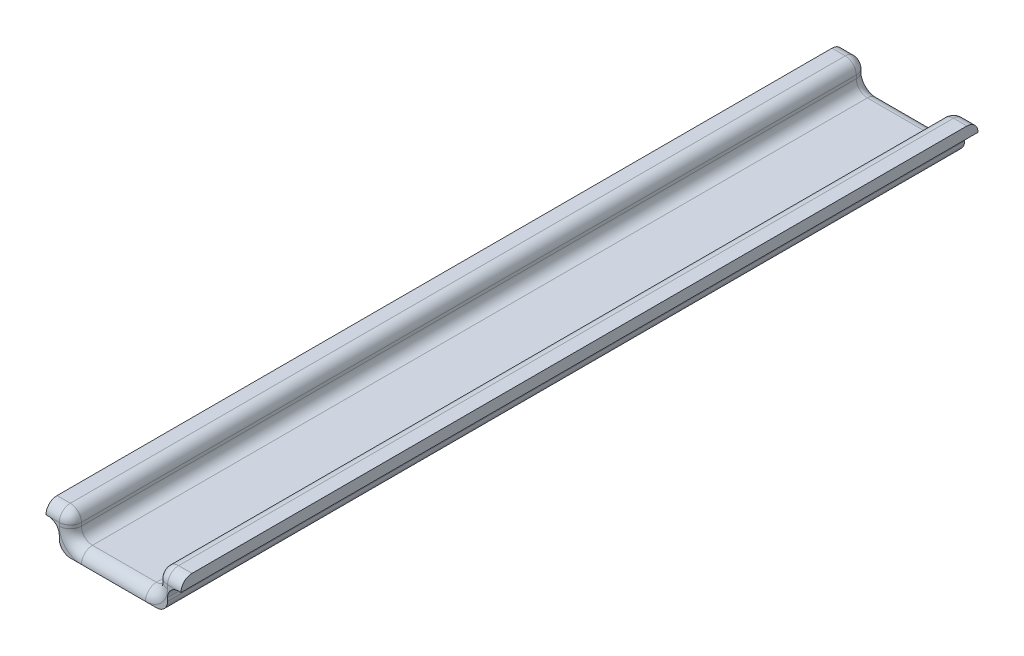
SolidWorks part; units mm, degrees
ref_plane "Front Plane" through (0, 0, 0) normal (0, 0, 1) x (1, 0, 0)
ref_plane "Top Plane" through (0, 0, 0) normal (0, 1, 0) x (1, 0, 0)
ref_plane "Right Plane" through (0, 0, 0) normal (1, 0, 0) x (0, 0, -1)
sketch "Sketch2" plane through (0, 0, 0) normal (0, 0, 1) x (1, 0, 0)
  line L0 (-9.2285, 0) -> (15.6196, 0)
  line L1 (15.6196, 0) -> (15.6196, 5.8485)
  line L2 (15.6196, 5.8485) -> (18.6948, 5.8485)
  line L3 (-9.2285, 0) -> (-9.2285, 5.817)
  line L4 (-9.2285, 5.817) -> (-12.2747, 5.817)
  dimension "D1" = 5.817
  dimension "D2" = 3.0752
  dimension "D3" = 5.8485
  dimension "D4" = 3.0463
  dimension "D5" = 24.8481
extrude "Extrude-Thin2" add sketch "Sketch2" along normal blind 180.34 and the other way blind 2.54 thin thin type one direction wall 2.54
fillet "Fillet1" radius 2.54 8 edges at (13.0796, 5.4643, 180.34) (13.0796, 5.4643, -2.54) (-6.6885, 5.4485, 180.34) (-6.6885, 5.4485, -2.54) (13.0796, 2.54, 88.9) (3.1956, 2.54, 180.34) (-6.6885, 2.54, 88.9) (3.1956, 2.54, -2.54)
fillet "Fillet2" radius 2.54 1 edges at (15.6196, 5.8485, 88.9)
fillet "Fillet3" radius 2.54 1 edges at (13.0796, 8.3885, 88.9) type face fillet first side face at (15.6227, 8.3885, 88.9) second side face at (13.0796, 6.7343, 88.9)
fillet "Fillet4" radius 2.54 1 edges at (15.6196, 0, 88.9) type face fillet first side face at (15.6196, 1.6543, 88.9) second side face at (3.1956, 0, 88.9)
fillet "Fillet5" radius 2.54 1 edges at (-6.6885, 8.357, 88.9) type face fillet first side face at (-6.6885, 6.7185, 88.9) second side face at (-9.2219, 8.357, 88.9)
fillet "Fillet6" radius 2.54 1 edges at (-9.2285, 0, 88.9) type face fillet first side face at (-9.2285, 3.6323, 88.9) second side face at (2.5606, 0, 88.9)
fillet "Fillet7" radius 2.54 1 edges at (-9.2285, 5.817, 88.9) type face fillet first side face at (-10.7516, 5.817, 88.9) second side face at (-9.2285, 4.479, 88.9)
